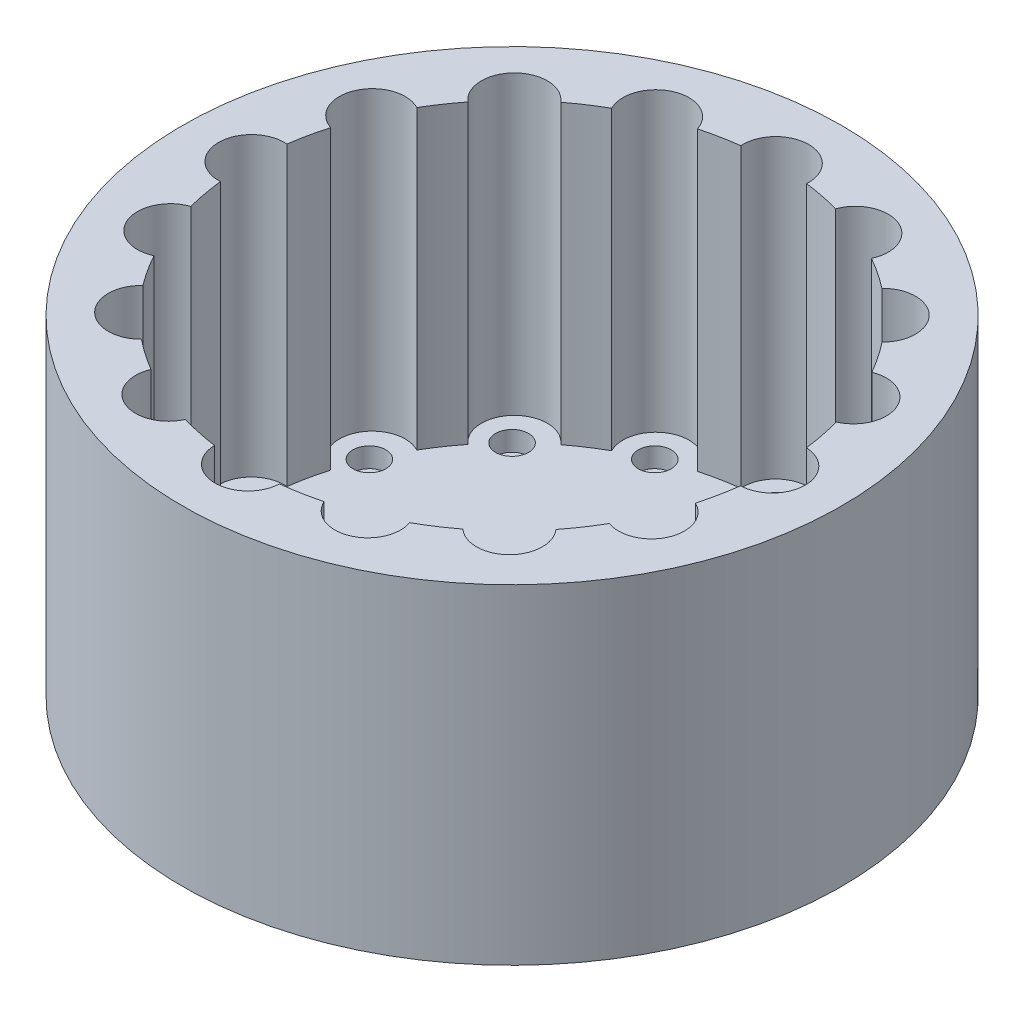
SolidWorks part; units mm, degrees
ref_plane "Front Plane" through (0, 0, 0) normal (0, 0, 1) x (1, 0, 0)
ref_plane "Top Plane" through (0, 0, 0) normal (0, 1, 0) x (1, 0, 0)
ref_plane "Right Plane" through (0, 0, 0) normal (1, 0, 0) x (0, 0, -1)
sketch "Sketch1" plane through (0, 0, 0) normal (0, 1, 0) x (1, 0, 0)
  arc A0 (-38.4721, 10.9498) -> (-39.6225, 5.4827) centre (0, 0) ccw
  arc A1 (4.9902, 39.6875) -> (-4.9902, 39.6875) centre (0, 40) ccw
  arc A2 (19.7423, 34.7885) -> (10.5038, 38.5963) centre (15.1971, 36.8722) ccw
  arc A3 (31.5425, 24.5981) -> (24.4561, 31.6528) centre (28.0405, 28.1668) ccw
  arc A4 (38.5639, 10.6218) -> (34.7247, 19.8543) centre (36.5748, 15.2091) ccw
  arc A5 (39.6831, -5.0248) -> (39.6903, 4.9683) centre (39.5008, -0.0281) ccw
  arc A6 (34.6812, -19.9303) -> (38.5373, -10.718) centre (36.373, -15.2253) ccw
  arc A7 (24.305, -31.769) -> (31.416, -24.7596) centre (27.6676, -28.0686) ccw
  arc A8 (10.1649, -38.6869) -> (19.4331, -34.9622) centre (14.7099, -36.6029) ccw
  arc A9 (-5.5266, -39.6164) -> (4.4678, -39.7497) centre (-0.5273, -39.5289) ccw
  arc A10 (-20.3279, -34.4496) -> (-11.148, -38.4151) centre (-15.7245, -36.4011) ccw
  arc A11 (-31.9737, -24.0351) -> (-25.0145, -31.2134) centre (-28.5678, -27.6957) ccw
  arc A12 (-38.7274, -10.0096) -> (-35.0397, -19.2929) centre (-37.1021, -14.7381) ccw
  arc A13 (-39.6225, 5.4827) -> (-39.7469, -4.4929) centre (-40.0281, 0.4992) ccw
  arc A14 (-34.5711, 20.1207) -> (-38.4721, 10.9498) centre (-36.9003, 15.6963) ccw
  arc A15 (-24.3492, 31.7351) -> (-31.4368, 24.7331) centre (-28.1949, 28.5397) ccw
  arc A16 (-10.477, 38.6035) -> (-19.6974, 34.814) centre (-15.2373, 37.074) ccw
  circle A17 centre (0, 0) radius 50
  arc A18 (-31.4368, 24.7331) -> (-34.5711, 20.1207) centre (0, 0) ccw
  arc A19 (-19.6974, 34.814) -> (-24.3492, 31.7351) centre (0, 0) ccw
  arc A20 (-4.9902, 39.6875) -> (-10.477, 38.6035) centre (0, 0) ccw
  arc A21 (10.5038, 38.5963) -> (4.9902, 39.6875) centre (0, 0) ccw
  arc A22 (24.4561, 31.6528) -> (19.7423, 34.7885) centre (0, 0) ccw
  arc A23 (34.7247, 19.8543) -> (31.5425, 24.5981) centre (0, 0) ccw
  arc A24 (39.6903, 4.9683) -> (38.5639, 10.6218) centre (0, 0) ccw
  arc A25 (38.5373, -10.718) -> (39.6831, -5.0248) centre (0, 0) ccw
  arc A26 (31.416, -24.7596) -> (34.6812, -19.9303) centre (0, 0) ccw
  arc A27 (19.4331, -34.9622) -> (24.305, -31.769) centre (0, 0) ccw
  arc A28 (-11.148, -38.4151) -> (-5.5266, -39.6164) centre (0, 0) ccw
  arc A29 (-25.0145, -31.2134) -> (-20.3279, -34.4496) centre (0, 0) ccw
  arc A30 (-35.0397, -19.2929) -> (-31.9737, -24.0351) centre (0, 0) ccw
  arc A31 (-39.7469, -4.4929) -> (-38.7274, -10.0096) centre (0, 0) ccw
  arc A32 (4.4678, -39.7497) -> (10.1649, -38.6869) centre (0, 0) ccw
  point P38 (-0.2637, 0.2355)
  dimension "D1" = 16
  dimension "D2" = 100
  dimension "D3" = 5
extrude "Boss-Extrude1" add sketch "Sketch1" along normal blind 45
sketch "Sketch2" plane through (0, 0, 0) normal (0, -1, 0) x (1, 0, 0)
  circle A0 centre (0, 0) radius 50
extrude "Boss-Extrude2" add sketch "Sketch2" along normal blind 5
sketch "Sketch3" plane through (0, 0, 0) normal (0, 1, 0) x (1, 0, 0)
  circle A0 centre (0, 40) radius 2.5
  circle A1 centre (15.3073, 36.9552) radius 2.5
  circle A2 centre (28.2843, 28.2843) radius 2.5
  circle A3 centre (36.9552, 15.3073) radius 2.5
  circle A4 centre (40, 0) radius 2.5
  circle A5 centre (36.9552, -15.3073) radius 2.5
  circle A6 centre (28.2843, -28.2843) radius 2.5
  circle A7 centre (15.3073, -36.9552) radius 2.5
  circle A8 centre (0, -40) radius 2.5
  circle A9 centre (-15.3073, -36.9552) radius 2.5
  circle A10 centre (-28.2843, -28.2843) radius 2.5
  circle A11 centre (-36.9552, -15.3073) radius 2.5
  circle A12 centre (-40, 0) radius 2.5
  circle A13 centre (-36.9552, 15.3073) radius 2.5
  circle A14 centre (-28.2843, 28.2843) radius 2.5
  circle A15 centre (-15.3073, 36.9552) radius 2.5
  point P35 (0, 0)
  dimension "D1" = 5
  dimension "D2" = 16
extrude "Cut-Extrude1" cut sketch "Sketch3" against normal blind 3
